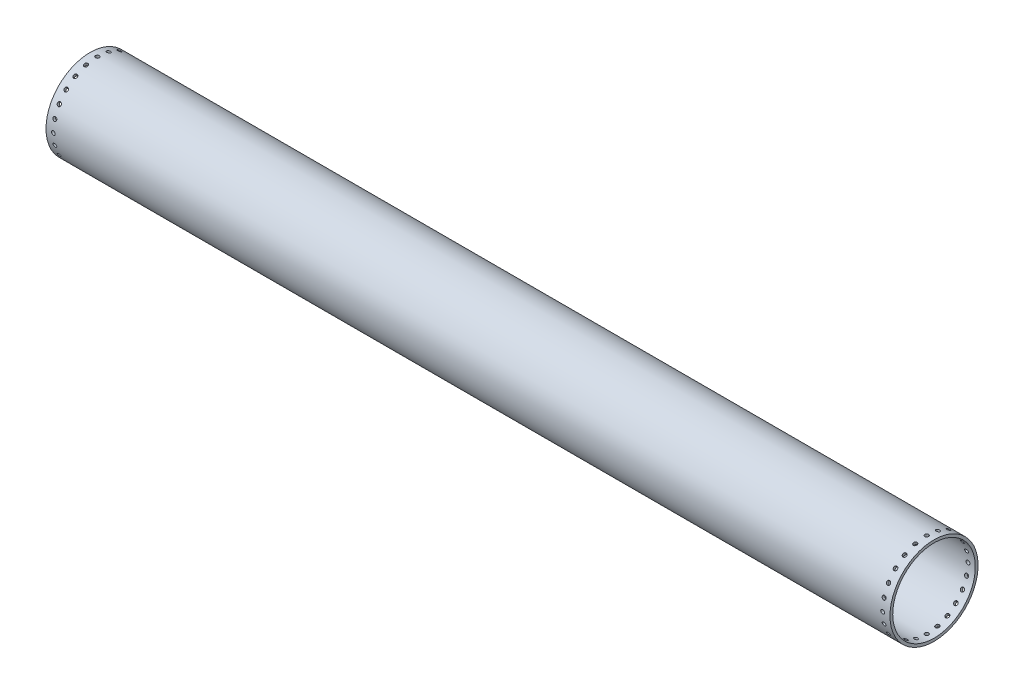
SolidWorks part; units mm, degrees
ref_plane "Front Plane" through (0, 0, 0) normal (0, 0, 1) x (1, 0, 0)
ref_plane "Top Plane" through (0, 0, 0) normal (0, 1, 0) x (1, 0, 0)
ref_plane "Right Plane" through (0, 0, 0) normal (1, 0, 0) x (0, 0, -1)
sketch "Tube Sketch" plane through (0, 0, 0) normal (0, 0, 1) x (1, 0, 0)
  line L0 (-1000, 0) -> (1000, 0) construction
  line L1 (0, 71.425) -> (1459.688, 71.425)
  line L2 (1459.688, 71.425) -> (1459.688, 76.2)
  line L3 (1459.688, 76.2) -> (0, 76.2)
  line L4 (0, 76.2) -> (0, 71.425)
revolve "Tube" add sketch "Tube Sketch" angle 360 about L0
ref_axis "Engine Axis" through (1532.6724, 0, 0) along (-1, 0, 0)
ref_plane "Bottom End" through (1459.688, 0, 0) normal (1, 0, 0) x (0, 0, -1)
sketch "Top Screw Hole Sketch" plane through (0, 0, 0) normal (0, 0, 1) x (1, 0, 0)
  line L0 (12.7, 51.425) -> (12.7, 96.2) construction
  line L1 (12.7, 70.425) -> (16, 70.425)
  line L2 (16, 70.425) -> (16, 77.2)
  line L3 (16, 77.2) -> (12.7, 77.2)
  line L4 (12.7, 77.2) -> (12.7, 70.425)
revolve "Top Screw Hole" cut sketch "Top Screw Hole Sketch" angle 360 about L0
pattern_circular "Top Screw Holes x24" count 24 over 360 about axis through (1532.6724, 0, 0) along (-1, 0, 0) of "Top Screw Hole"
sketch "Bottom Screw Hole Sketch" plane through (0, 0, 0) normal (0, 0, 1) x (1, 0, 0)
  line L0 (1446.988, 51.425) -> (1446.988, 96.2) construction
  line L1 (1446.988, 70.425) -> (1450.288, 70.425)
  line L2 (1450.288, 70.425) -> (1450.288, 77.2)
  line L3 (1450.288, 77.2) -> (1446.988, 77.2)
  line L4 (1446.988, 77.2) -> (1446.988, 70.425)
revolve "Bottom Screw Hole" cut sketch "Bottom Screw Hole Sketch" angle 360 about L0
pattern_circular "Bottom Screw Holes x24" count 24 over 360 about axis through (1532.6724, 0, 0) along (-1, 0, 0) of "Bottom Screw Hole"
